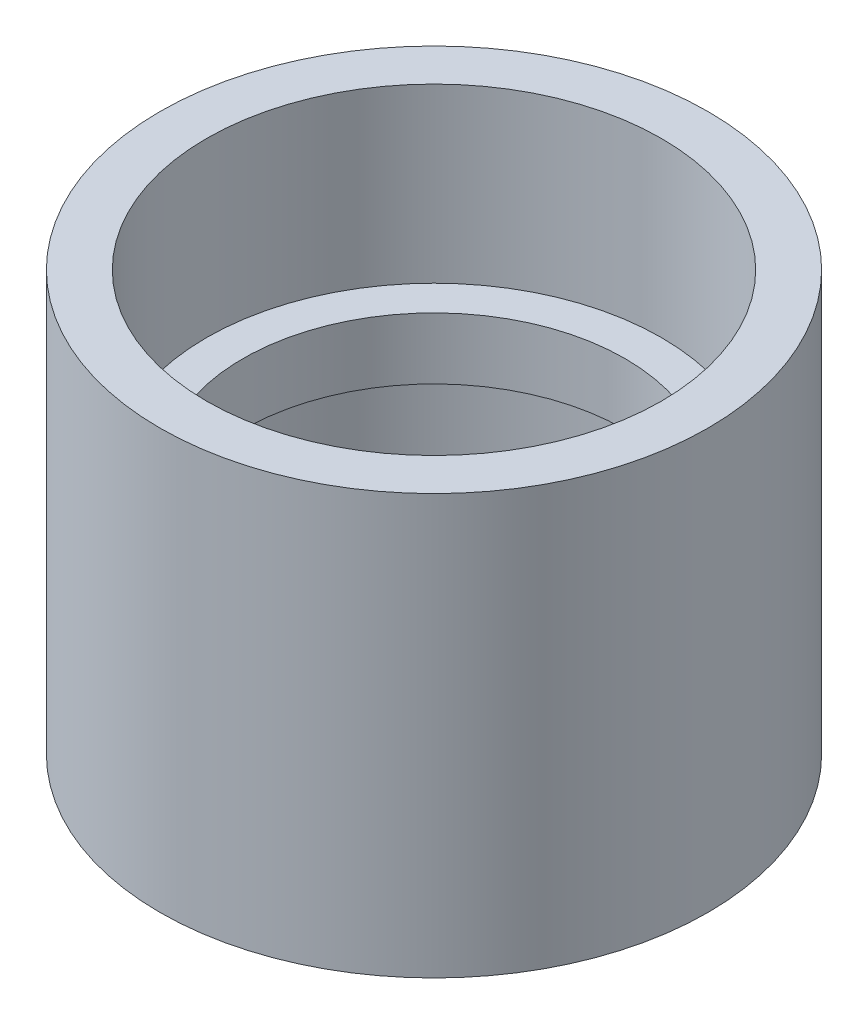
SolidWorks part; units mm, degrees
other "Markup1"
sketch "Sketch29" plane through (63.2714, 21.9964, 116.8802) normal (1, 0, 0) x (0, 0, 1)
material "6061-T6 (SS)"
ref_plane "X-Y Datum" through (0, 0, 0) normal (0, 0, 1) x (1, 0, 0)
ref_plane "X-Z Datum" through (0, 0, 0) normal (0, 1, 0) x (1, 0, 0)
ref_plane "Y-Z Datum" through (0, 0, 0) normal (1, 0, 0) x (0, 0, -1)
sketch "Main skeleton" plane through (0, 0, 0) normal (1, 0, 0) x (0, 0, -1)
  line L0 (0, 0) -> (-39.9854, 0) construction
  line L1 (0, 0) -> (0, -60.6196) construction
  line L2 (0, 21.9964) -> (-30.2613, 21.9964) construction
  line L3 (-84.7344, 21.9964) -> (-84.7344, -57.7596) construction
  line L4 (69.85, 21.9964) -> (69.85, -22.7076) construction
  line L5 (58.6559, -10.541) -> (-36.2694, -10.541) construction
  line L6 (69.85, -22.7076) -> (-84.7344, -57.7596) construction
  line L7 (27.94, -25.5016) -> (27.94, -201.1028) construction
  circle A0 centre (-84.7344, -57.7596) radius 10.3251 construction
  circle A1 centre (69.85, -22.7076) radius 10.3251 construction
  point P7 (-84.7344, 21.9964)
  point P12 (69.85, 21.9964)
  point P19 (27.94, -66.9036)
  point P20 (0, 0)
  dimension "D4" = 20.6502
  dimension "D1" = 21.9964
  dimension "D2" = 84.7344
  dimension "D3" = 79.756
  dimension "D5" = 69.85
  dimension "D6" = 44.704
  dimension "D7" = 32.5374
  dimension "D8" = 27.94
  dimension "D9" = 88.9
ref_plane "Toe Bracket Plane" through (0, 0, -27.94) normal (0, 0, 1) x (1, 0, 0)
sketch "Toe Bracket Sketch" plane through (0, 0, -27.94) normal (0, 0, 1) x (1, 0, 0)
  line L0 (0, -66.9036) -> (-65.278, -66.9036) construction
  dimension "D1" = 65.278
ref_plane "Back of Upright" through (0, -10.541, 0) normal (0, -1, 0) x (-1, 0, 0)
ref_plane "Plane2" through (0, -57.7596, 84.7344) normal (0, -1, 0) x (-1, 0, 0)
sketch "Caster Angle" plane through (0, -57.7596, 84.7344) normal (0, -1, 0) x (-1, 0, 0)
  line L0 (0, 0) -> (2.959, 0) construction
  line L1 (0, 154.5844) -> (-2.4392, 154.5844) construction
  line L2 (-2.4392, 154.5844) -> (2.959, 0) construction
  line L3 (0, 200084.7344) -> (0, -199945.5269) construction
  point P6 (0, 0)
  point P15 (0, 84.7344)
  dimension "D1" = 2
ref_plane "Caster Plane" through (0, 0, 0) normal (0.9994, 0, 0.0349) x (0.0349, 0, -0.9994)
sketch "UBJ LBJ Caster" plane through (0, 0, 0) normal (0.9994, 0, 0.0349) x (0.0349, 0, -0.9994)
  circle A0 centre (-84.786, -57.7596) radius 10.3251 construction
  circle A1 centre (69.8074, -22.7076) radius 10.3251 construction
  dimension "D1" = 20.6502
  dimension "D2" = 20.6502
sketch "Brake Tabs" plane through (0, -10.541, 0) normal (0, -1, 0) x (-1, 0, 0)
  line L0 (0, 0) -> (-55.6175, -1.9422) construction
  line L1 (-2.4392, 69.85) -> (2.959, -84.7344) construction
  line L2 (-57.2927, 46.0282) -> (-53.9423, -49.9126) construction
  point P9 (-55.6175, -1.9422)
  dimension "D1" = 55.6514
  dimension "D2" = 95.9993
sketch "Main Body" plane through (0, -10.541, 0) normal (0, -1, 0) x (-1, 0, 0)
  line L0 (36.9042, 5.6919) -> (24.0965, 88.7327)
  line L1 (-30.2275, 86.8357) -> (24.0965, 88.7327)
  line L2 (71.628, 16.8275) -> (53.848, 16.8275)
  line L3 (71.628, 39.0525) -> (53.848, 39.0525)
  line L4 (-2.4392, 69.85) -> (2.959, -84.7344) construction
  line L5 (-30.2275, 86.8357) -> (-37.2113, 3.1037)
  line L7 (20.7672, 60.329) -> (-24.9249, 58.7334)
  line L8 (0, 27.94) -> (65.278, 27.94) construction
  line L15 (-23.1965, 79.4565) -> (17.5974, 80.8811)
  line L16 (65.278, 39.0525) -> (65.278, 16.8275) construction
  line L17 (20.7672, 60.329) -> (17.5974, 80.8811)
  line L18 (-24.9249, 58.7334) -> (-23.1965, 79.4565)
  line L19 (-2.4392, 69.85) -> (-2.0789, 59.5312) construction
  line L20 (-2.4392, 69.85) -> (-2.7996, 80.1688) construction
  line L21 (23.5731, 42.1363) -> (21.9369, 52.7452)
  line L22 (21.9369, 52.7452) -> (-25.5628, 51.0865)
  line L23 (-25.5628, 51.0865) -> (-26.455, 40.3893)
  line L24 (0, 200000) -> (0, -200030.2613) construction
  line L25 (71.628, 39.0525) -> (71.628, 44.1325)
  line L26 (71.628, 44.1325) -> (44.6271, 44.1325)
  line L27 (71.628, 16.8275) -> (71.628, 11.7475)
  line L28 (71.628, 11.7475) -> (46.1421, 11.7475)
  line L29 (37.0998, -4.2332) -> (24.3747, -115.7559)
  line L30 (-36.7141, -6.8109) -> (-16.2406, -117.1742)
  line L31 (24.3747, -115.7559) -> (-16.2406, -117.1742)
  line L32 (25.2152, -41.1747) -> (22.6433, -63.7146)
  line L33 (-22.2816, -42.8333) -> (-18.1437, -65.1389)
  line L34 (22.6433, -63.7146) -> (-18.1437, -65.1389)
  line L35 (-47.2194, -55.3475) -> (-35.8532, -41.2874)
  line L36 (-50.3895, 51.2323) -> (-41.5847, 39.5527)
  line L37 (-61.9097, -46.5573) -> (-47.2691, -11.7926)
  line L38 (-65.0065, 42.1253) -> (-47.9766, 8.4665)
  circle A0 centre (0, 0) radius 30.9905
  circle A1 centre (0, 0) radius 26.0375
  circle A2 centre (0, 0) radius 37.3405
  arc A3 (53.848, 16.8275) -> (53.848, 39.0525) centre (53.848, 27.94) cw
  arc A4 (23.5731, 42.1363) -> (14.0429, 34.5993) centre (16.6698, 41.0716) cw
  arc A5 (-26.455, 40.3893) -> (-16.4222, 33.5355) centre (-19.4942, 39.8087) ccw
  arc A6 (44.6271, 44.1325) -> (32.4395, 38.7599) centre (44.6271, 27.6225) ccw
  arc A7 (32.4395, 38.7599) -> (14.0429, 34.5993) centre (20.2519, 49.8973) cw
  arc A8 (46.1421, 11.7475) -> (37.2691, 2.308) centre (46.1421, 2.8575) ccw
  arc A9 (25.2152, -41.1747) -> (15.3954, -34.0191) centre (18.2752, -40.3828) ccw
  arc A10 (-22.2816, -42.8333) -> (-12.9848, -35.0102) centre (-15.4138, -41.5592) cw
  circle A11 centre (-53.9423, -49.9126) radius 4.2
  circle A12 centre (-57.2927, 46.0282) radius 4.2
  arc A13 (-47.2194, -55.3475) -> (-61.9097, -46.5573) centre (-53.9423, -49.9126) cw
  arc A14 (-50.3895, 51.2323) -> (-65.0065, 42.1253) centre (-57.2927, 46.0282) ccw
  arc A15 (-35.8532, -41.2874) -> (-12.9848, -35.0102) centre (-20.0509, -54.062) cw
  arc A16 (-41.5847, 39.5527) -> (-16.4222, 33.5355) centre (-25.3588, 51.7848) ccw
  arc A17 (-47.2691, -11.7926) -> (-47.9766, 8.4665) centre (-69.5075, -2.4273) ccw
  point P14 (-2.0789, 59.5312)
  point P19 (-3.0655, 87.7842)
  point P20 (-2.7996, 80.1688)
  point P35 (-1.8129, 51.9158)
  point P36 (65.278, 27.94)
  point P40 (65.278, 27.94)
  point P60 (4.067, -116.4651)
  point P64 (2.2498, -64.4268)
  point P81 (-47.2634, -11.9034)
  point P85 (0, 0)
  dimension "D4" = 20.6502
  dimension "D1" = 61.9811
  dimension "D16" = 6.985
  dimension "D14" = 16.51
  dimension "D17" = 8.89
  dimension "D22" = 6.985
  dimension "D23" = 8.4
  dimension "D26" = 20.32
  dimension "D27" = 24.13
  dimension "D2" = 6.35
  dimension "D3" = 4.953
  dimension "D6" = 7.62
  dimension "D7" = 7.62
  dimension "D8" = 7.62
  dimension "D5" = 22.86
  dimension "D10" = 22.225
  dimension "D11" = 65.278
  dimension "D12" = 6.35
  dimension "D13" = 11.43
  dimension "D15" = 5.08
  dimension "D18" = 31.75
  dimension "D19" = 20.32
  dimension "D20" = 7.62
  dimension "D21" = 20.32
  dimension "D24" = 4.445
  dimension "D25" = 4.445
  dimension "D28" = 37.7218
extrude "Boss-Extrude1" add sketch "Main Body" along normal blind 57.15 contours A0 A1 | A2 A0 region at (-36.0752, -10.541, -3.8908) region at (30.114, -10.541, 0)
extrude "Cut-Extrude2" cut sketch "Main Body<5>" along normal blind 23.495 contours A0 A1 region at (30.114, -10.541, 0)
sketch "Main Body<5>" plane through (0, -10.541, 0) normal (0, -1, 0) x (-1, 0, 0) same geometry as "Main Body"
extrude "Cut-Extrude3" cut sketch "Main Body<6>" against normal blind 25.273 from surface contours A0 A1 region at (30.114, -10.541, 0) starting at face at (0, -67.691, -26.0375)
sketch "Main Body<6>" plane through (0, -10.541, 0) normal (0, -1, 0) x (-1, 0, 0) same geometry as "Main Body"
equation "\"upper ball joint X\"= 3.14in"
equation "\"upper ball joint Y\"= 3.336"
equation "\"lower ball joint X\"= 1.76"
equation "\"lower ball joint Y\"= 2.75in"
equation "\"D3@Main skeleton\"=\"upper ball joint X\""
equation "\"D2@Main skeleton\"=\"upper ball joint Y\""
equation "\"D5@Main skeleton\"=\"lower ball joint Y\""
equation "\"D6@Main skeleton\"=\"lower ball joint X\""
equation "\"wheel offset to back of upright\"= 1.281in"
equation "\"D7@Main skeleton\"=\"wheel offset to back of upright\""
equation "\"Toe bracket distance from center Z\"= 1.1"
equation "\"D8@Main skeleton\"=\"Toe bracket distance from center Z\""
equation "\"Toe bracket distance from hub face Y\"= 3.5in"
equation "\"D9@Main skeleton\"=\"Toe bracket distance from hub face Y\""
equation "\"Toe Bracket distance in X\"= 2.57in"
equation "\"Caster\"= 2.5deg"
equation "\"Spacing Between UBJ/LBJ\"= 0.813in"
equation "\"Toe Bracket Spacing\"= 0.875in"
equation "\"D4@Main skeleton\"=\"Spacing Between UBJ/LBJ\""
equation "\"1/4 bolt\"= .25in"
equation "\"3/8 Bolt\"= 5 / 16"
equation "\"Back of upright face LBJ 1\"= .5in"
equation "\"Back of upright face LBJ 2\"= .9in"
equation "\"Back of upright face UBJ 1\"= .9in"
equation "\"UBJ Y1\"= 1in"
equation "\"UBJ Y2\"= .5in"
equation "\"LBJ Double shear thickness\"= .275in"
equation "\"LBJ fucking slant shit\"= .03in"
equation "\"Brake mounting holes parallel\"= 03.7795in"
equation "\"Brake mounting holes normal\"= 02.191in"
equation "\"Speed sensor radial distance\"= 01.835in"
equation "\"Speed sensor hold diameter\"= 0.46875in"
equation "\"D1@UBJ LBJ Caster\" = \"Spacing Between UBJ/LBJ\""
equation "\"D2@UBJ LBJ Caster\" = \"Spacing Between UBJ/LBJ\""
equation "\"D1@Toe Bracket Sketch\" = \"Toe Bracket distance in X\""
equation "\"D1@Brake Tabs\" = \"Brake mounting holes normal\""
equation "\"D2@Brake Tabs\" = \"Brake mounting holes parallel\""
equation "\"D4@Main Body\"=\"Spacing Between UBJ/LBJ\""
equation "\"D10@Main Body\"=\"Toe Bracket Spacing\""
equation "\"D11@Main Body\"=\"Toe Bracket distance in X\""
